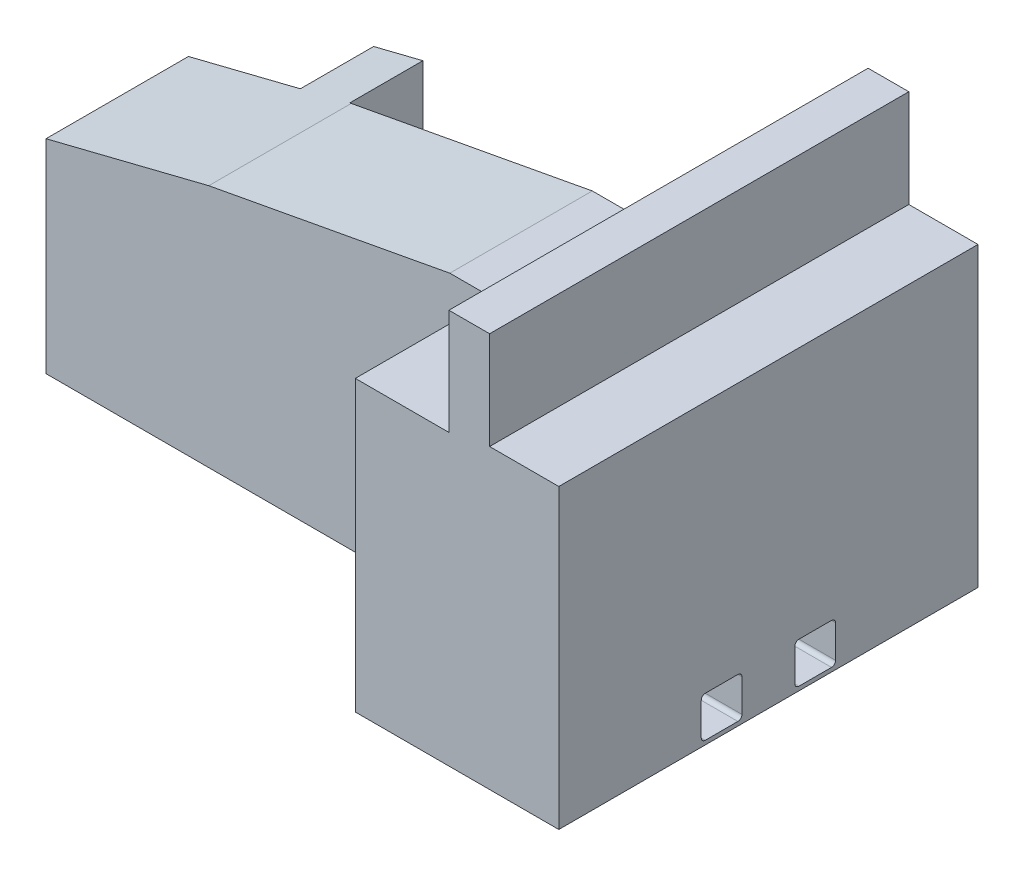
SolidWorks part; units mm, degrees
material "Custom Plastic"
ref_plane "Front Plane" through (0, 0, 0) normal (0, 0, 1) x (1, 0, 0)
ref_plane "Top Plane" through (0, 0, 0) normal (0, 1, 0) x (1, 0, 0)
ref_plane "Right Plane" through (0, 0, 0) normal (1, 0, 0) x (0, 0, -1)
sketch "Sketch1" plane through (0, 0, 0) normal (0, 0, 1) x (1, 0, 0)
  line L0 (-800, 0) -> (800, 0)
  line L1 (-800, 0) -> (-800, 500)
  line L2 (-400, 0) -> (-400, 600)
  line L3 (530, 0) -> (530, 970)
  line L4 (300, 0) -> (300, 730)
  line L5 (-800, 500) -> (-400, 600)
  line L6 (-400, 600) -> (300, 730)
  line L7 (300, 730) -> (530, 970)
  line L8 (800, 0) -> (530, 970)
  line L9 (-800, 500) -> (-800, 970)
  line L10 (-800, 970) -> (530, 970)
  dimension "D1" = 1600
  dimension "D2" = 500
  dimension "D3" = 400
  dimension "D4" = 800
  dimension "D5" = 600
  dimension "D6" = 270
  dimension "D7" = 500
  dimension "D8" = 970
  dimension "D9" = 730
sketch "Sketch2" plane through (0, 0, 0) normal (0, 1, 0) x (1, 0, 0)
  line L0 (800, -515) -> (800, 515)
  line L2 (800, -515) -> (300, -515)
  line L3 (300, -515) -> (300, -175)
  line L4 (300, -175) -> (-800, -175)
  line L5 (-800, -175) -> (-800, 175)
  line L6 (-800, 175) -> (-404, 175)
  line L7 (-404, 175) -> (-404, 355)
  line L8 (-404, 355) -> (-525, 355)
  line L9 (-525, 355) -> (-525, 175)
  line L10 (-525, 175) -> (300, 175)
  line L11 (300, 175) -> (300, 515)
  line L12 (300, 515) -> (800, 515)
  dimension "D1" = 800
  dimension "D2" = 500
  dimension "D3" = 175
  dimension "D4" = 175
  dimension "D5" = 530
  dimension "D6" = 121
  dimension "D7" = 500
  dimension "D8" = 350
  dimension "D9" = 1600
  dimension "D10" = 1030
  dimension "D11" = 515
  dimension "D12" = 275
extrude "Boss-Extrude1" add sketch "Sketch2" along normal blind 970 contours L12 L11 L10 L6 L5 L4 L3 L2 L0 | L8 L9 L6 L7 region at (207.7778, 0, 0) region at (-464.5, 0, -265)
extrude "Cut-Extrude1" cut sketch "Sketch1" against normal through all both and the other way through all contours L10 L9 L5 L6 L7 region at (-263.3113, 797.1661, 0)
sketch "Sketch3" plane through (-800, 0, 0) normal (-1, 0, 0) x (0, 0, 1)
  line L0 (-165, 0) -> (-65, 0)
  line L1 (175, 0) -> (-175, 0) construction
  line L2 (-55, 10) -> (-55, 120)
  line L3 (-55, 120) -> (-175, 120)
  line L4 (-175, 730) -> (-175, 0) construction
  line L5 (-175, 120) -> (-175, 10)
  line L11 (-165, 100) -> (-165, 20)
  line L12 (-155, 10) -> (-75, 10)
  line L13 (-65, 20) -> (-65, 100)
  line L14 (-75, 110) -> (-155, 110)
  line L19 (0, 137.8655) -> (0, -90.7951) construction
  line L20 (75, 110) -> (155, 110)
  line L21 (65, 20) -> (65, 100)
  line L22 (155, 10) -> (75, 10)
  line L23 (165, 100) -> (165, 20)
  line L24 (175, 120) -> (175, 10)
  line L25 (55, 120) -> (175, 120)
  line L26 (55, 10) -> (55, 120)
  line L27 (165, 0) -> (65, 0)
  arc A0 (175, 10) -> (165, 0) centre (165, 10) cw
  arc A1 (155, 10) -> (165, 20) centre (155, 20) ccw
  arc A2 (65, 20) -> (75, 10) centre (75, 20) ccw
  arc A3 (55, 10) -> (65, 0) centre (65, 10) ccw
  arc A4 (-65, 0) -> (-55, 10) centre (-65, 10) ccw
  arc A5 (-165, 0) -> (-175, 10) centre (-165, 10) cw
  arc A6 (-165, 20) -> (-155, 10) centre (-155, 20) ccw
  arc A7 (-75, 10) -> (-65, 20) centre (-75, 20) ccw
  arc A8 (-65, 100) -> (-75, 110) centre (-75, 100) ccw
  arc A9 (-165, 100) -> (-155, 110) centre (-155, 100) cw
  arc A10 (155, 110) -> (165, 100) centre (155, 100) cw
  arc A11 (75, 110) -> (65, 100) centre (75, 100) ccw
  point P27 (175, 0)
  point P30 (165, 10)
  point P33 (65, 10)
  point P36 (55, 0)
  point P39 (-55, 0)
  point P42 (-175, 0)
  point P45 (-165, 10)
  point P48 (-65, 10)
  point P51 (-65, 110)
  point P54 (-165, 110)
  point P57 (165, 110)
  point P60 (65, 110)
  dimension "D3" = 10
  dimension "D4" = 10
  dimension "D1" = 120
  dimension "D2" = 120
  dimension "D5" = 100
  dimension "D6" = 100
  dimension "D8" = 10
  dimension "D9" = 10
extrude "Cut-Extrude5" cut sketch "Sketch3" against normal blind 1625 contours A9 L11 A6 L12 A7 L13 A8 L14 | L21 A2 L22 A1 L23 L20 region at (-800, 60, -115) region at (-800, 60, 115)
sketch "Sketch4" plane through (0, 0, 0) normal (0, -1, 0) x (1, 0, 0)
  line L0 (-1069.2255, 0) -> (880.5229, 0) construction
  line L1 (0, 391.8823) -> (0, -321.383) construction
  line L2 (300, 175) -> (-800, 175) construction
  line L3 (-800, -175) -> (-525, -175) construction
  circle A0 centre (-498.5, 115) radius 8.5
  circle A1 centre (-501, -115) radius 8.5
  circle A2 centre (501, -115) radius 8.5
  circle A3 centre (498.5, 115) radius 8.5
  dimension "D1" = 17
  dimension "D4" = 17
  dimension "D2" = 498.5
  dimension "D3" = 60
  dimension "D5" = 501
  dimension "D6" = 60
extrude "Cut-Extrude6" cut sketch "Sketch4" against normal blind 78
sketch "Sketch5" plane through (0, 0, 515) normal (0, 0, 1) x (1, 0, 0)
  line L1 (800, 970) -> (800, 0) construction
  line L3 (800, 970) -> (530, 970) construction
  line L4 (630, 970) -> (530, 970)
  line L5 (530, 970) -> (530, 710)
  line L6 (530, 710) -> (155, 710)
  line L7 (800, 0) -> (300, 0) construction
  line L9 (155, 650) -> (155, 710)
  line L10 (800, 730) -> (630, 730)
  line L11 (800, 730) -> (800, 650)
  line L12 (630, 970) -> (630, 730)
  line L13 (155, 650) -> (800, 650)
  line L14 (155, 710) -> (155, 970)
  line L15 (155, 970) -> (800, 970)
  line L16 (800, 970) -> (800, 730)
  line M1 (530, 970) -> (300, 730)
  line M2 (300, 730) -> (300, 0)
  line M4 (800, 0) -> (800, 970)
  line M5 (800, 970) -> (530, 970)
  dimension "D1" = 170
  dimension "D2" = 100
  dimension "D3" = 375
  dimension "D4" = 710
  dimension "D5" = 650
  dimension "D6" = 730
extrude "Cut-Extrude8" cut sketch "Sketch5" against normal blind 1478 contours L15 L14 L6 M2 M1 | L6 L5 M1 M2 | L12 L10 M5 M4 region at (715, 850, 515) region at (290.5475, 861.1332, 515) region at (447.8571, 797.1429, 515)
